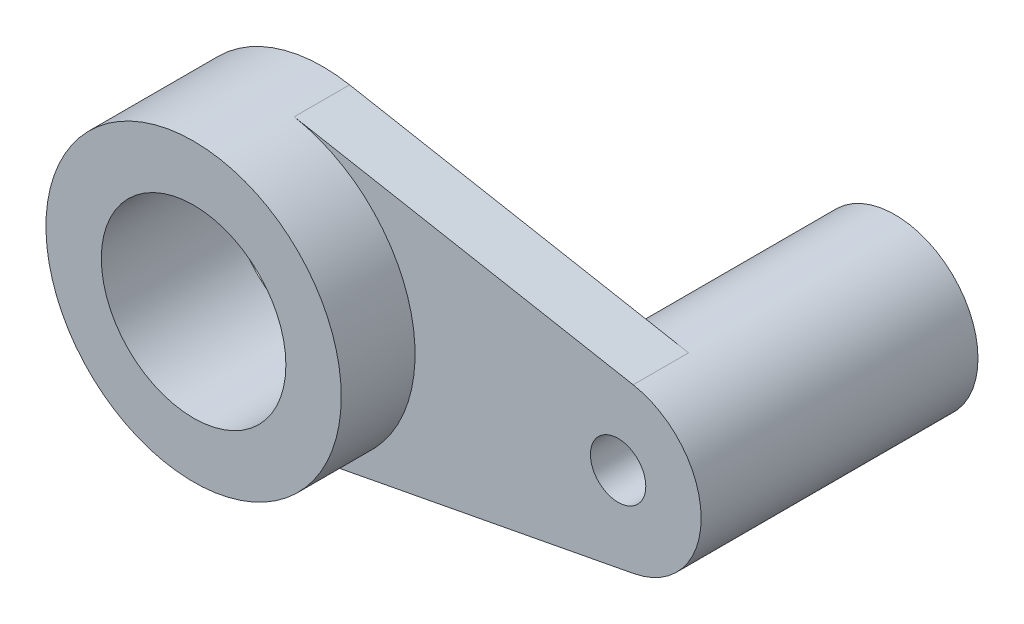
SolidWorks part; units mm, degrees
material "Galvanized Steel"
ref_plane "Front Plane" through (0, 0, 0) normal (0, 0, 1) x (1, 0, 0)
ref_plane "Top Plane" through (0, 0, 0) normal (0, 1, 0) x (1, 0, 0)
ref_plane "Right Plane" through (0, 0, 0) normal (1, 0, 0) x (0, 0, -1)
sketch "Croquis1" plane through (0, 0, 0) normal (0, 0, 1) x (1, 0, 0)
  line L0 (-52.3347, 32.3264) -> (-15.606, 25.5441)
  line L1 (-52.2509, 0.8741) -> (-15.5588, 7.8522)
  circle A0 centre (-55.2402, 16.5924) radius 10
  circle A1 centre (-55.2402, 16.5924) radius 16
  circle A2 centre (-17.2403, 16.6937) radius 3
  circle A3 centre (-17.2403, 16.6937) radius 9
  dimension "D1" = 20
  dimension "D2" = 32
  dimension "D3" = 6
  dimension "D4" = 18
  dimension "D5" = 38
extrude "Saliente-Extruir1" add sketch "Croquis1" along normal blind 14 contours A1 | A0
extrude "Saliente-Extruir2" add sketch "Croquis1<3>" along normal blind 6 contours A3 L0 A1 L1 | A3 A2 region at (-33.3152, 16.6509, 0) region at (-10.5183, 22.2881, 0)
sketch "Croquis1<3>" plane through (0, 0, 0) normal (0, 0, 1) x (1, 0, 0) same geometry as "Croquis1"
extrude "Saliente-Extruir3" add sketch "Croquis1<4>" against normal blind 24 contours A3 A2 region at (-10.5183, 22.2881, 0)
sketch "Croquis1<4>" plane through (0, 0, 0) normal (0, 0, 1) x (1, 0, 0) same geometry as "Croquis1"
